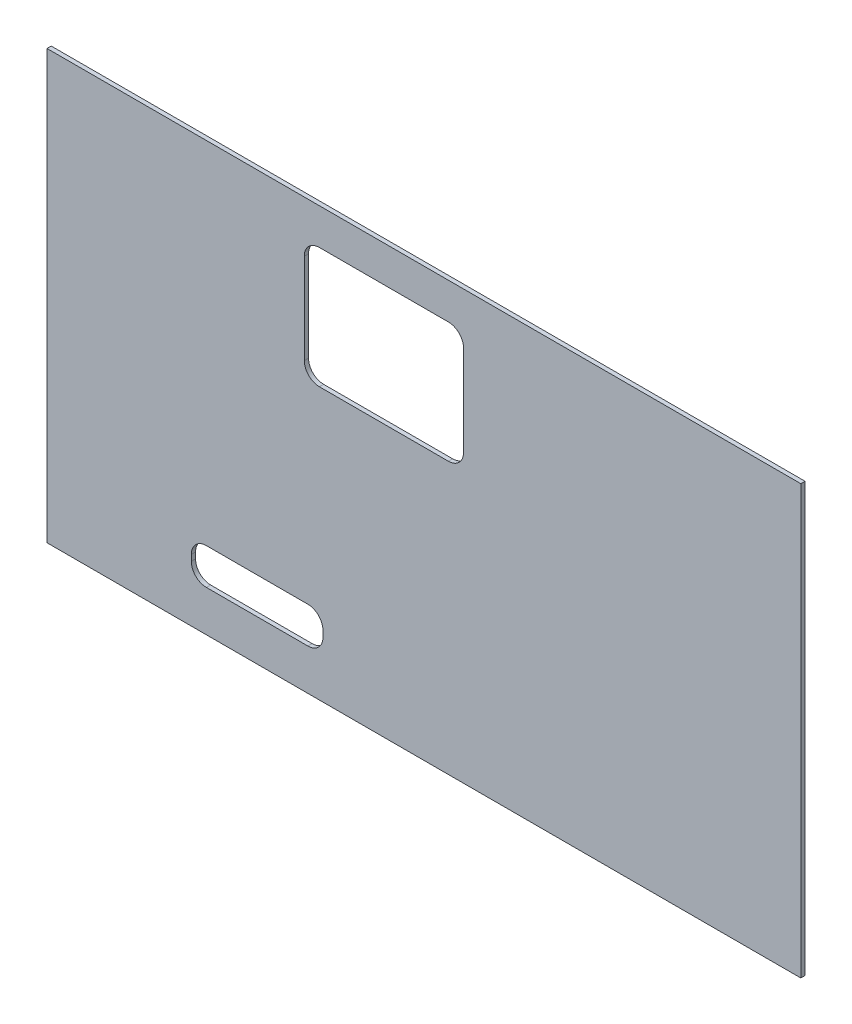
SolidWorks part; units mm, degrees
ref_plane "Front Plane" through (0, 0, 0) normal (0, 0, 1) x (1, 0, 0)
ref_plane "Top Plane" through (0, 0, 0) normal (0, 1, 0) x (1, 0, 0)
ref_plane "Right Plane" through (0, 0, 0) normal (1, 0, 0) x (0, 0, -1)
sketch "Sketch2" plane through (0, 0, 0) normal (0, 0, 1) x (1, 0, 0)
  line L0 (9, -6) -> (19, -6)
  line L1 (0, 0) -> (125.0228, 0)
  line L2 (0, 0) -> (0, -71)
  line L3 (0, -71) -> (125.0228, -71)
  line L4 (125.0228, 0) -> (125.0228, -71)
  line L5 (9, -6) -> (14, -18)
  line L6 (14, -18) -> (19, -6)
  line L7 (4, -6) -> (4, -17)
  line L8 (4, -17) -> (11.25, -34.4)
  line L9 (11.25, -34.4) -> (11.25, -23.4)
  line L10 (11.25, -23.4) -> (4, -6)
  line L11 (24, -6) -> (24, -17)
  line L12 (24, -17) -> (16.75, -34.4)
  line L13 (16.75, -34.4) -> (16.75, -23.4)
  line L14 (16.75, -23.4) -> (24, -6)
  line L15 (24, -6) -> (42.6775, -6)
  line L16 (0, 0) -> (4, 0)
  line L17 (0, 0) -> (0, -6)
  line L20 (16.75, -58.1932) -> (16.75, -71)
  line L21 (16.75, -58.1932) -> (23.9424, -58.1932)
  line L22 (23.9424, -58.1932) -> (45.7691, -58.1932)
  line L23 (23.9424, -58.1932) -> (23.9424, -64.1932)
  line L24 (23.9424, -64.1932) -> (45.7691, -64.1932)
  line L25 (45.7691, -64.1932) -> (45.7691, -58.1932)
  line L26 (42.6775, -6) -> (69.0876, -6)
  line L27 (42.6775, -6) -> (42.6775, -26)
  line L28 (42.6775, -26) -> (69.0876, -26)
  line L29 (69.0876, -26) -> (69.0876, -6)
  line L30 (69.0876, -6) -> (100.1386, -6)
  line L31 (112.8886, -34.4) -> (112.8886, -23.4)
  line L32 (100.1386, -17) -> (107.3886, -34.4)
  line L33 (105.1386, -6) -> (110.1386, -18)
  line L34 (100.1386, -6) -> (100.1386, -17)
  line L35 (120.1386, -17) -> (112.8886, -34.4)
  line L36 (120.1386, -6) -> (120.1386, -17)
  line L37 (107.3886, -23.4) -> (100.1386, -6)
  line L38 (105.1386, -6) -> (115.1386, -6)
  line L39 (112.8886, -23.4) -> (120.1386, -6)
  line L40 (110.1386, -18) -> (115.1386, -6)
  line L41 (107.3886, -34.4) -> (107.3886, -23.4)
  line L42 (113.0586, -33.55) -> (113.0586, -23.434)
  line L43 (113.0586, -23.434) -> (119.9686, -6.85)
  line L44 (119.9686, -6.85) -> (119.9686, -16.966)
  line L45 (119.9686, -16.966) -> (113.0586, -33.55)
  line L46 (100.3086, -16.966) -> (107.2186, -33.55)
  line L47 (107.2186, -33.55) -> (107.2186, -23.434)
  line L48 (107.2186, -23.434) -> (100.3086, -6.85)
  line L49 (100.3086, -6.85) -> (100.3086, -16.966)
  line L50 (105.3936, -6.17) -> (110.1386, -17.558)
  line L51 (110.1386, -17.558) -> (114.8836, -6.17)
  line L52 (105.3936, -6.17) -> (114.8836, -6.17)
  line L53 (9.255, -6.17) -> (18.745, -6.17)
  line L54 (14, -17.558) -> (18.745, -6.17)
  line L55 (9.255, -6.17) -> (14, -17.558)
  line L56 (4.17, -6.85) -> (4.17, -16.966)
  line L57 (4.17, -16.966) -> (11.08, -33.55)
  line L58 (11.08, -33.55) -> (11.08, -23.434)
  line L59 (11.08, -23.434) -> (4.17, -6.85)
  line L60 (23.83, -6.85) -> (23.83, -16.966)
  line L61 (23.83, -16.966) -> (16.92, -33.55)
  line L62 (16.92, -33.55) -> (16.92, -23.434)
  line L63 (16.92, -23.434) -> (23.83, -6.85)
  point P8 (14, -6)
  point P20 (16.75, -58.1932)
  point P35 (110.1386, -6)
  dimension "D1" = 125.0228
  dimension "D2" = 71
  dimension "D3" = 10
  dimension "D4" = 11
  dimension "D5" = 0.17
  dimension "D7" = 18.6775
  dimension "D8" = 12.8068
  dimension "D9" = 7.1924
  dimension "D10" = 21.8267
  dimension "D11" = 6
  dimension "D12" = 26.4101
  dimension "D13" = 20
  dimension "D14" = 31.051
  dimension "D15" = 10
  dimension "D16" = 11
extrude "Boss-Extrude5" add sketch "Sketch2" along normal blind 0.7 contours L25 L24 L23 L3 L4 L1 L2 L22 L41 L32 L34 L29 L28 L27 L11 L12 L13 L14 L26 L37 L40 L33 L38 L10 L9 L8 L7 L6 L5 L0 L31 L39 L36 L35 | L14 L13 L12 L11 L62 L63 L60 L61 | L9 L10 L7 L8 L59 L58 L57 L56 | L5 L6 L0 L55 L53 L54 | L39 L31 L35 L36 L44 L45 L42 L43 | L33 L40 L38 L50 L52 L51 | L32 L41 L37 L34 L49 L48 L47 L46 | L53 L54 L55 | L56 L57 L58 L59 | L60 L61 L62 L63 | L50 L51 L52 | L42 L43 L44 L45 | L46 L47 L48 L49 region at (14, -6.1562, 0) region at (63.4521, -37.4124, 0) region at (7.5979, -14.7113, 0) region at (23.9707, -11.5, 0) region at (103.7366, -14.7113, 0) region at (112.9179, -28.9, 0) region at (110.1386, -6.1562, 0)
extrude "Boss-Extrude6" add sketch "Sketch2<9>" against normal blind 5 contours L53 L55 L54 | L63 L62 L61 L60 | L58 L59 L56 L57 | L48 L49 L46 L47 | L52 L50 L51 | L45 L44 L43 L42 region at (116.5136, -20.2, 0) region at (103.7636, -20.2, 0) region at (110.1386, -9.966, 0) region at (14, -9.966, 0) region at (7.625, -20.2, 0) region at (20.375, -20.2, 0)
sketch "Sketch2<9>" plane through (0, 0, 0) normal (0, 0, 1) x (1, 0, 0) same geometry as "Sketch2"
fillet "Fillet1" radius 2.5 8 edges at (23.9424, -64.1932, 0.35) (45.7691, -64.1932, 0.35) (45.7691, -58.1932, 0.35) (23.9424, -58.1932, 0.35) (42.6775, -6, 0.35) (69.0876, -6, 0.35) (42.6775, -26, 0.35) (69.0876, -26, 0.35)
